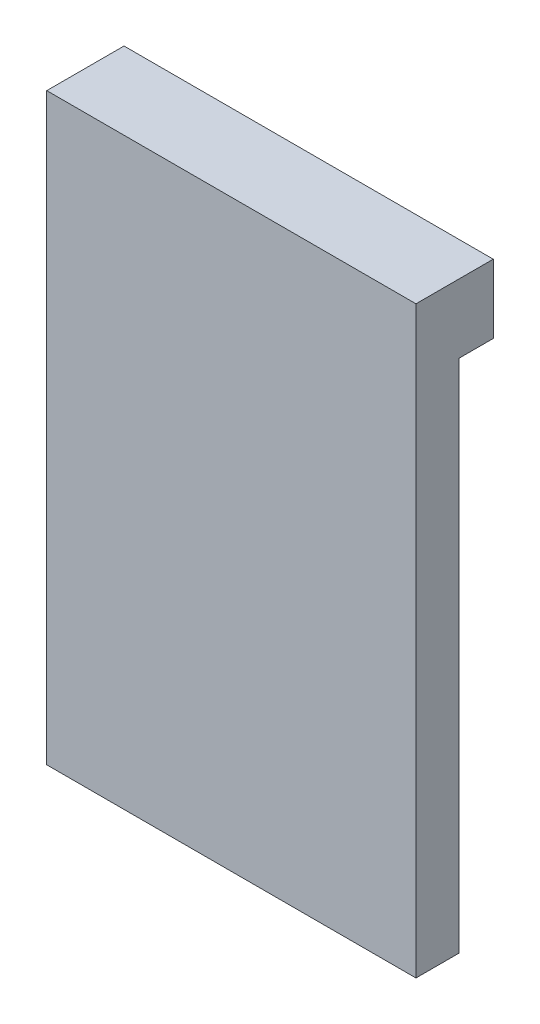
SolidWorks part; units mm, degrees
ref_plane "Ön Düzlem" through (0, 0, 0) normal (0, 0, 1) x (1, 0, 0)
ref_plane "Üst Düzlem" through (0, 0, 0) normal (0, 1, 0) x (1, 0, 0)
ref_plane "Sağ Düzlem" through (0, 0, 0) normal (1, 0, 0) x (0, 0, -1)
sketch "sase_taban1" plane through (0, 0, 0) normal (0, 0, 1) x (1, 0, 0)
  line L0 (-41.0184, -30.1425) -> (44.9816, -30.1425)
  line L1 (-38.0184, 102.8575) -> (41.9816, 102.8575)
  line L2 (-38.0184, 102.8575) -> (-38.0184, -27.1425)
  line L3 (-38.0184, -27.1425) -> (41.9816, -27.1425)
  line L4 (41.9816, 102.8575) -> (41.9816, -27.1425)
  line L5 (44.9816, 105.8575) -> (44.9816, -30.1425)
  line L6 (-41.0184, 105.8575) -> (44.9816, 105.8575)
  line L7 (-41.0184, 105.8575) -> (-41.0184, -30.1425)
extrude "Yükseklik-Ekstrüzyon4" add sketch "sase_taban1" against normal blind 3 contours L4 L1 L2 L3 region at (1.9816, 37.8575, 0)
extrude "Yükseklik-Ekstrüzyon5" add sketch "sase_taban1<5>" against normal blind 10 contours L6 L7 L0 L5 L1 L4 L3 L2 region at (-39.4093, 37.8575, 0)
sketch "sase_taban1<5>" plane through (0, 0, 0) normal (0, 0, 1) x (1, 0, 0) same geometry as "sase_taban1"
sketch "sase_eklem1" plane through (44.9816, 0, 0) normal (1, 0, 0) x (0, 0, -1)
  line L0 (18, 105.8575) -> (0, 105.8575)
  line L1 (18, 105.8575) -> (18, 102.8575)
  line L2 (18, 89.8575) -> (10, 89.8575)
  line L3 (10, 89.8575) -> (0, 97.8575)
  line L4 (0, 105.8575) -> (0, -30.1425) construction
  line L5 (18, 89.8575) -> (18, 92.8575)
  line L7 (0, 105.8575) -> (0, 97.8575)
  line L9 (10, 105.8575) -> (10, -30.1425) construction
  arc A0 (18, 102.8575) -> (18, 92.8575) centre (18, 97.8575) ccw
extrude "Yükseklik-Ekstrüzyon6" add sketch "sase_eklem1" against normal up to surface (86 mm away) up to face at (-41.0184, 37.8575, -5)
sketch "eklem_orta" plane through (0, 89.8575, 0) normal (0, -1, 0) x (1, 0, 0)
  line L0 (-16.0184, -18) -> (-16.0184, -3)
  line L1 (-16.0184, -3) -> (19.9816, -3)
  line L7 (-16.0184, -18) -> (19.9816, -18)
  line L8 (19.9816, -3) -> (19.9816, -18)
  line L9 (-41.0184, -18) -> (44.9816, -18) construction
extrude "Kes-Ekstrüzyon1" cut sketch "eklem_orta" against normal up to vertex (13 mm away) up to point (44.9816, 102.8575, -18)
sketch "eklem_kablo" plane through (19.9816, 0, 0) normal (-1, 0, 0) x (0, 0, 1)
  line L4 (-10, 89.8575) -> (0, 97.8575) construction
  line L7 (-5, 93.8575) -> (-8.1235, 91.3587)
  arc A1 (-13.6699, 100.3575) -> (-13.6699, 95.3575) centre (-18, 97.8575) cw
  arc A3 (-13.6699, 100.3575) -> (-5, 93.8575) centre (-12.5849, 92.7725) cw
  arc A4 (-13.6699, 95.3575) -> (-8.1235, 91.3587) centre (-12.8961, 90.5849) cw
  line M1 (-10, 89.8575) -> (-3, 95.4575)
  arc M4 (-18, 102.8575) -> (-18, 92.8575) centre (-18, 97.8575) cw
extrude "Kes-Ekstrüzyon3" cut sketch "eklem_kablo" along normal blind 42
extrude "Kes-Ekstrüzyon4" cut sketch "eklem_kablo<2>" against normal blind 6 contours A4 A3 M4 M1 region at (19.9816, 96.4644, -9.3225)
sketch "eklem_kablo<2>" plane through (19.9816, 0, 0) normal (-1, 0, 0) x (0, 0, 1) same geometry as "eklem_kablo"
sketch "eklem_sag_kapak" plane through (-41.0184, 0, 0) normal (-1, 0, 0) x (0, 0, 1)
  line L0 (-18, 102.8575) -> (-18, 92.8575)
  arc A0 (-18, 102.8575) -> (-18, 92.8575) centre (-18, 97.8575) cw
extrude "Yükseklik-Ekstrüzyon7" add sketch "eklem_sag_kapak" against normal blind 3
sketch "eklem_sol_kapak" plane through (44.9816, 0, 0) normal (1, 0, 0) x (0, 0, -1)
  line L0 (18, 102.8575) -> (18, 92.8575)
  arc A0 (18, 102.8575) -> (18, 92.8575) centre (18, 97.8575) ccw
extrude "Yükseklik-Ekstrüzyon8" add sketch "eklem_sol_kapak" against normal blind 3
